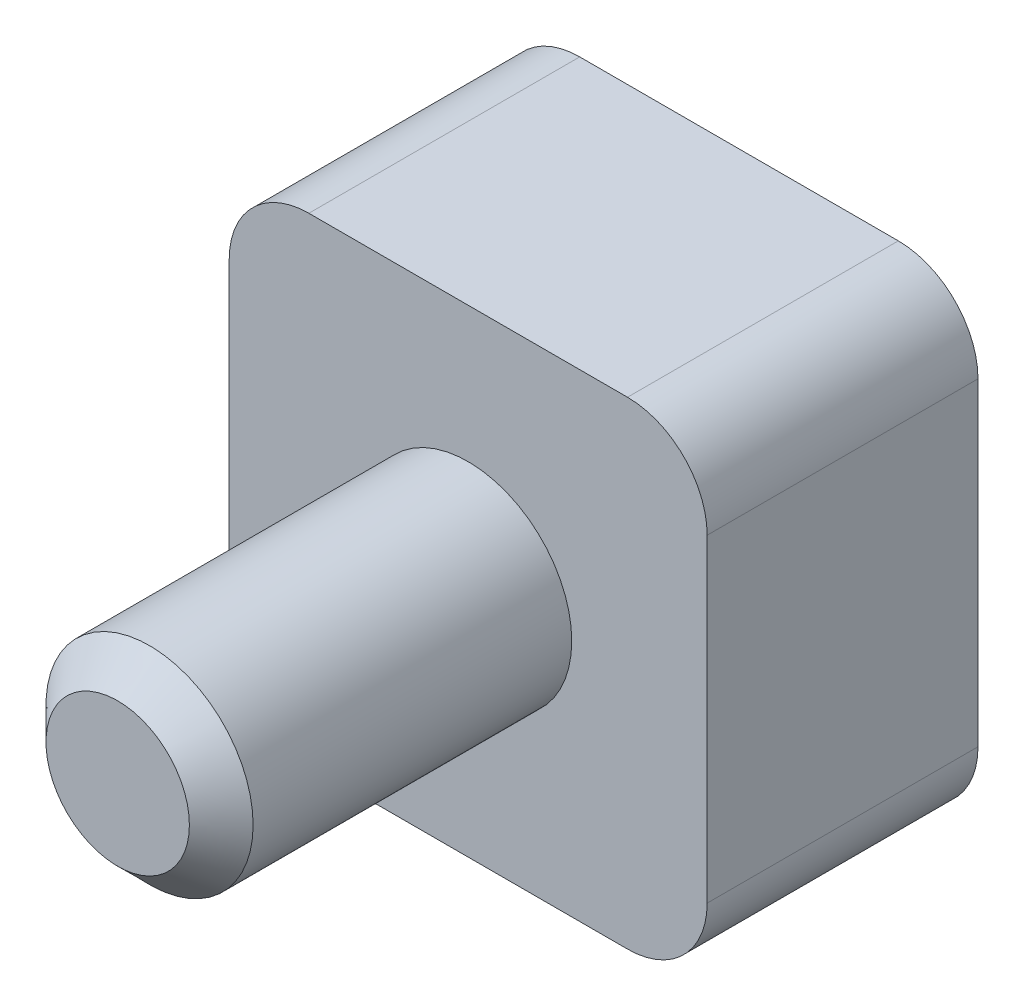
SolidWorks part; units mm, degrees
ref_plane "Top Plane" through (0, 0, 0) normal (0, 0, 1) x (1, 0, 0)
ref_plane "Right Plane" through (0, 0, 0) normal (0, 1, 0) x (1, 0, 0)
ref_plane "Front Plane" through (0, 0, 0) normal (1, 0, 0) x (0, 0, -1)
sketch "Sketch1" plane through (0, 0, 0) normal (0, 0, 1) x (1, 0, 0)
  line L0 (5, 6.5) -> (-5, 6.5) construction
  line L1 (5, -7.5) -> (-5, -7.5)
  line L2 (7.5, -5) -> (7.5, 5)
  line L3 (5, 7.5) -> (-5, 7.5)
  line L4 (-7.5, -5) -> (-7.5, 5)
  line L5 (7.5, -7.5) -> (-7.5, 7.5) construction
  line L6 (7.5, 7.5) -> (-7.5, -7.5) construction
  line L7 (-6.5, -5) -> (-6.5, 5) construction
  line L8 (5, -6.5) -> (-5, -6.5) construction
  line L9 (6.5, -5) -> (6.5, 5) construction
  line L10 (-5, 3.25) -> (-6.5, 3.25) construction
  line L11 (-3.25, 5) -> (-3.25, 6.5) construction
  line L12 (3.25, 5) -> (3.25, 6.5)
  line L13 (5, 3.25) -> (6.5, 3.25)
  line L14 (5, -3.25) -> (6.5, -3.25) construction
  line L15 (3.25, -5) -> (3.25, -6.5) construction
  line L16 (-3.25, -5) -> (-3.25, -6.5)
  line L17 (-5, -3.25) -> (-6.5, -3.25)
  line L18 (-3.25, -6.5) -> (5, -6.5)
  line L19 (6.5, 3.25) -> (6.5, -5)
  line L20 (3.25, 6.5) -> (-5, 6.5)
  line L21 (-6.5, 5) -> (-6.5, -3.25)
  arc A0 (-5, -7.5) -> (-7.5, -5) centre (-5, -5) cw
  arc A1 (5, -7.5) -> (7.5, -5) centre (5, -5) ccw
  arc A2 (7.5, 5) -> (5, 7.5) centre (5, 5) ccw
  arc A3 (-5, 7.5) -> (-7.5, 5) centre (-5, 5) ccw
  arc A4 (-5, 6.5) -> (-6.5, 5) centre (-5, 5) ccw
  arc A5 (-5, -6.5) -> (-6.5, -5) centre (-5, -5) cw construction
  arc A6 (5, -6.5) -> (6.5, -5) centre (5, -5) ccw
  arc A7 (6.5, 5) -> (5, 6.5) centre (5, 5) ccw construction
  arc A8 (-5, 3.25) -> (-3.25, 5) centre (-5, 5) ccw construction
  arc A9 (3.25, 5) -> (5, 3.25) centre (5, 5) ccw
  arc A10 (5, -3.25) -> (3.25, -5) centre (5, -5) ccw construction
  arc A11 (-3.25, -5) -> (-5, -3.25) centre (-5, -5) ccw
  point P0 (0, 0)
  dimension "D2" = 2.5
  dimension "D4" = 3.5
  dimension "D1" = 15
  dimension "D3" = 1
extrude "Boss-Extrude1" add sketch "Sketch1" along normal blind 3
fillet "Fillet1" radius 1.5 4 edges at (-6.5, -3.25, 1.5) (-3.25, -6.5, 1.5) (6.5, 3.25, 1.5) (3.25, 6.5, 1.5)
sketch "Sketch3" plane through (0, 0, 3) normal (0, 0, 1) x (1, 0, 0)
  line L4 (-5, -7.5) -> (5, -7.5)
  line L5 (7.5, -5) -> (7.5, 5)
  line L6 (5, 7.5) -> (-5, 7.5)
  line L7 (-7.5, 5) -> (-7.5, -5)
  line L8 (-5, -7.5) -> (5, -7.5)
  line L9 (7.5, -5) -> (7.5, 5)
  line L10 (5, 7.5) -> (-5, 7.5)
  line L11 (-7.5, 5) -> (-7.5, -5)
  arc A4 (-7.5, -5) -> (-5, -7.5) centre (-5, -5) ccw
  arc A5 (5, -7.5) -> (7.5, -5) centre (5, -5) ccw
  arc A6 (7.5, 5) -> (5, 7.5) centre (5, 5) ccw
  arc A7 (-5, 7.5) -> (-7.5, 5) centre (-5, 5) ccw
  arc A8 (-7.5, -5) -> (-5, -7.5) centre (-5, -5) ccw
  arc A9 (5, -7.5) -> (7.5, -5) centre (5, -5) ccw
  arc A10 (7.5, 5) -> (5, 7.5) centre (5, 5) ccw
  arc A11 (-5, 7.5) -> (-7.5, 5) centre (-5, 5) ccw
  dimension "D1" = 0
extrude "Boss-Extrude2" add sketch "Sketch3" along normal blind 5.5
sketch "Sketch4" plane through (0, 0, 8.5) normal (0, 0, 1) x (1, 0, 0)
  circle A0 centre (0, 0) radius 3.25
  dimension "D1" = 6.5
extrude "Boss-Extrude3" add sketch "Sketch4" along normal blind 11
chamfer "Chamfer1" distance 1 angle 45 1 edges at (3.25, 0, 19.5)
